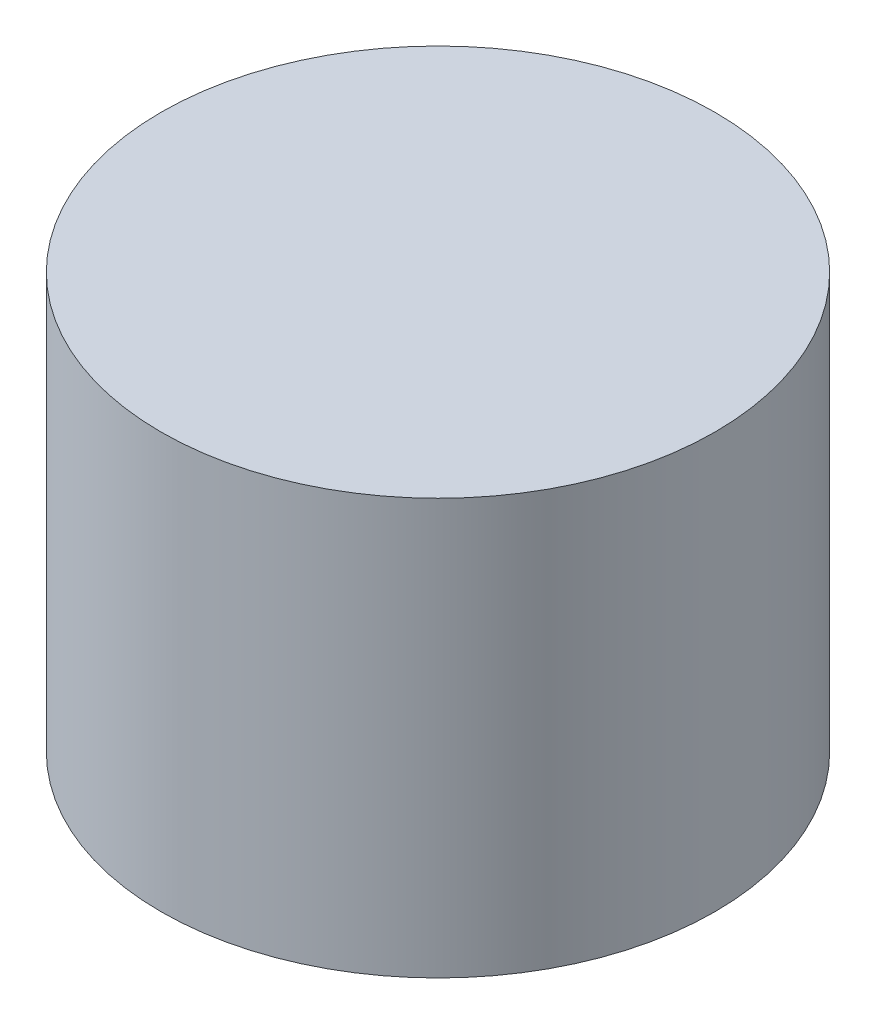
SolidWorks part; units mm, degrees
ref_plane "Front Plane" through (0, 0, 0) normal (0, 0, 1) x (1, 0, 0)
ref_plane "Top Plane" through (0, 0, 0) normal (0, 1, 0) x (1, 0, 0)
ref_plane "Right Plane" through (0, 0, 0) normal (1, 0, 0) x (0, 0, -1)
sketch "Sketch1" plane through (0, 0, 0) normal (0, 1, 0) x (1, 0, 0)
  circle A0 centre (0, 0) radius 4
  dimension "D1" = 8
extrude "Boss-Extrude1" add sketch "Sketch1" along normal blind 6
